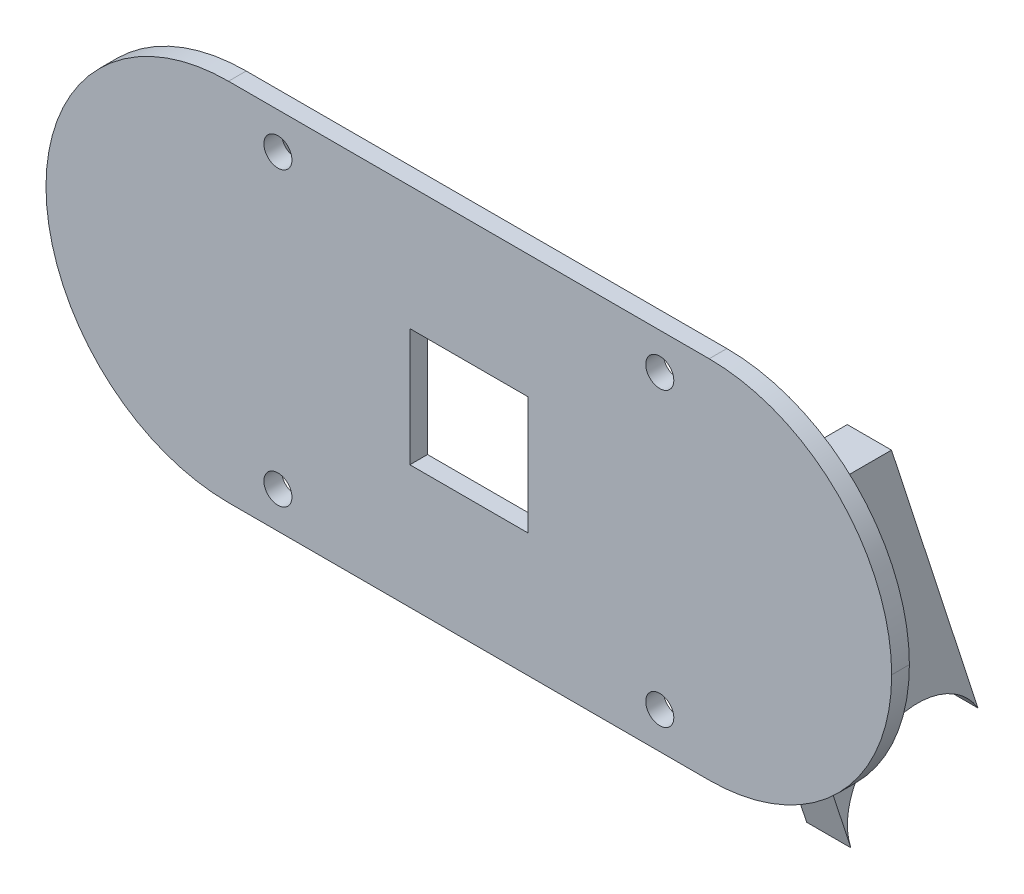
SolidWorks part; units mm, degrees
ref_plane "Front Plane" through (0, 0, 0) normal (0, 0, 1) x (1, 0, 0)
ref_plane "Top Plane" through (0, 0, 0) normal (0, 1, 0) x (1, 0, 0)
ref_plane "Right Plane" through (0, 0, 0) normal (1, 0, 0) x (0, 0, -1)
sketch "Sketch1" plane through (0, 0, 0) normal (0, 0, 1) x (1, 0, 0)
  line L0 (-43.18, 33.02) -> (43.18, 33.02) construction
  line L1 (-95.631, 41.275) -> (95.631, 41.275)
  line L2 (-95.631, 41.275) -> (-95.631, -41.275)
  line L3 (-95.631, -41.275) -> (95.631, -41.275)
  line L4 (95.631, 41.275) -> (95.631, -41.275)
  line L5 (-95.631, 41.275) -> (95.631, -41.275) construction
  line L6 (-95.631, -41.275) -> (95.631, 41.275) construction
  line L7 (43.18, 33.02) -> (43.18, -33.02) construction
  line L8 (43.18, -33.02) -> (-43.18, -33.02) construction
  line L9 (-43.18, -33.02) -> (-43.18, 33.02) construction
  line L10 (-43.18, -33.02) -> (43.18, 33.02) construction
  line L13 (-13.335, 13.335) -> (13.335, 13.335)
  line L14 (-13.335, 13.335) -> (-13.335, -13.335)
  line L15 (-13.335, -13.335) -> (13.335, -13.335)
  line L16 (13.335, 13.335) -> (13.335, -13.335)
  line L17 (-13.335, 13.335) -> (13.335, -13.335) construction
  line L18 (-13.335, -13.335) -> (13.335, 13.335) construction
  circle A0 centre (-43.18, 33.02) radius 3.175
  circle A1 centre (43.18, 33.02) radius 3.175
  circle A2 centre (43.18, -33.02) radius 3.175
  circle A3 centre (-43.18, -33.02) radius 3.175
  point P0 (0, 0)
  point P15 (0, 0)
  dimension "D3" = 86.36
  dimension "D5" = 6.35
  dimension "D6" = 26.67
  dimension "D1" = 191.262
  dimension "D2" = 82.55
  dimension "D4" = 66.04
  dimension "D7" = 26.67
extrude "Boss-Extrude1" add sketch "Sketch1" along normal blind 4
ref_plane "Plane1" through (71.59, 0, 0) normal (1, 0, 0) x (0, 0, -1)
sketch "Sketch2" plane through (71.59, 0, 0) normal (1, 0, 0) x (0, 0, -1)
  line L0 (0, 20) -> (20, 20)
  line L1 (20, 20) -> (39.5612, -40.3108)
  line L2 (0, -20) -> (10.7981, -53.2927)
  line L3 (0, -41.275) -> (0, 41.275) construction
  line L4 (0, 20) -> (0, -20)
  arc A0 (10.7981, -53.2927) -> (39.5612, -40.3108) centre (25.8987, -48.3949) cw
  dimension "D5" = 15.875
  dimension "D1" = 40
  dimension "D2" = 20
  dimension "D3" = 20
  dimension "D4" = 63.4038
  dimension "D7" = 35
fillet "Fillet5" radius 41.275 4 edges at (-95.631, -41.275, 2) (95.631, -41.275, 2) (95.631, 41.275, 2) (-95.631, 41.275, 2)
extrude "Boss-Extrude2" add sketch "Sketch2" against normal blind 10
pattern_linear "LPattern1" count 2 spacing 130 along (-1, 0, 0) of "Boss-Extrude2"
